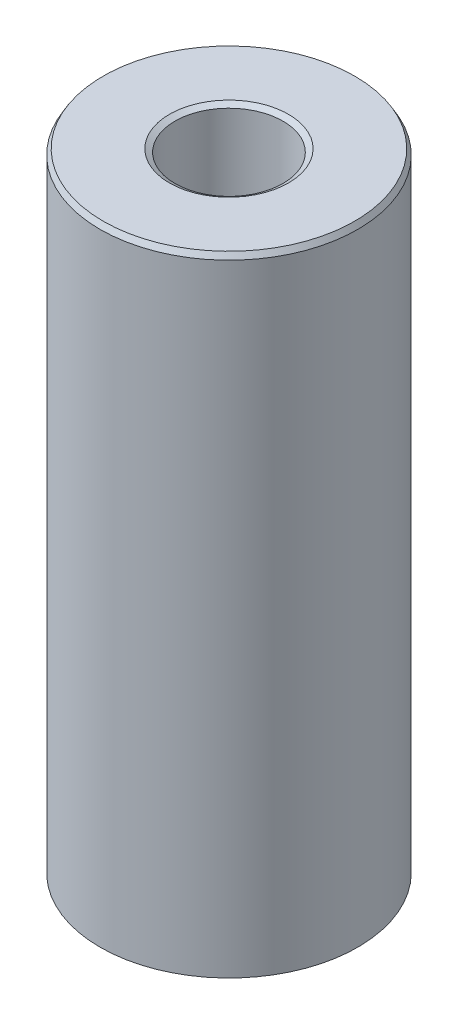
SolidWorks part; units mm, degrees
ref_plane "Front Plane" through (0, 0, 0) normal (0, 0, 1) x (1, 0, 0)
ref_plane "Top Plane" through (0, 0, 0) normal (0, 1, 0) x (1, 0, 0)
ref_plane "Right Plane" through (0, 0, 0) normal (1, 0, 0) x (0, 0, -1)
sketch "Sketch1" plane through (0, 0, 0) normal (0, 1, 0) x (1, 0, 0)
  circle A0 centre (0, 0) radius 47.5
  dimension "SLEEVE_OD" = 95
extrude "Boss-Extrude1" add sketch "Sketch1" along normal blind 232.2646
sketch "Sketch2" plane through (0, 0, 0) normal (0, 1, 0) x (1, 0, 0)
  circle A0 centre (0, 0) radius 19.9096
  dimension "BORE_D" = 39.8193
extrude "Cut-Extrude1" cut sketch "Sketch2" along normal through all
chamfer "Chamfer1" distance 2.0237 angle 30 4 edges at (0, 232.2646, 19.9096) (0, 0, 19.9096) (0, 0, 47.5) (0, 232.2646, 47.5) first distance on face at (0, 232.2646, 19.9096) first distance on face at (0, 0, 19.9096) first distance on face at (0, 232.2646, 47.5)
